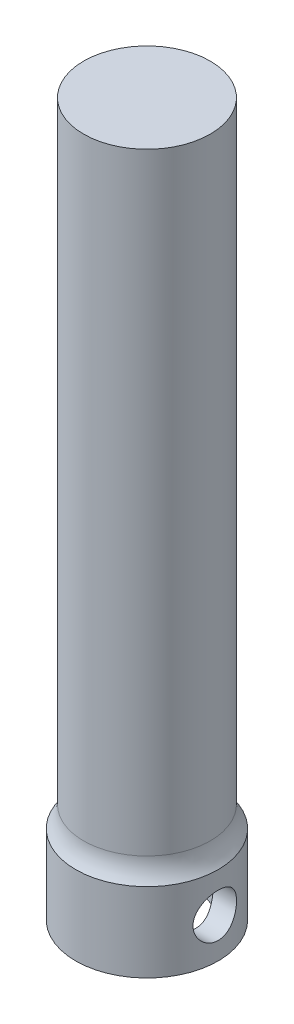
SolidWorks part; units mm, degrees
ref_plane "Front Plane" through (0, 0, 0) normal (0, 0, 1) x (1, 0, 0)
ref_plane "Top Plane" through (0, 0, 0) normal (0, 1, 0) x (1, 0, 0)
ref_plane "Right Plane" through (0, 0, 0) normal (1, 0, 0) x (0, 0, -1)
sketch "Sketch1" plane through (0, 0, 0) normal (0, 1, 0) x (1, 0, 0)
  line L0 (-4.0996, 3) -> (4.0996, 3)
  arc A0 (-4.0996, 3) -> (4.0996, 3) centre (0, 0) ccw
  dimension "D1" = 10.16
  dimension "D2" = 3
extrude "Boss-Extrude1" add sketch "Sketch1" along normal blind 57.15
sketch "Sketch3" plane through (0, 0, 0) normal (0, -1, 0) x (1, 0, 0)
  line L0 (-4.0996, -3) -> (4.0996, -3)
  arc A0 (-4.0996, -3) -> (4.0996, -3) centre (0, 0) ccw
extrude "Boss-Extrude2" add sketch "Sketch3" against normal up to surface (57.15 mm away) up to face at (0, 57.15, 1.04)
sketch "Sketch4" plane through (0, 57.15, 0) normal (0, 1, 0) x (1, 0, 0)
  line L1 (-4.0996, 3) -> (4.0996, 3)
  arc A0 (-4.0996, 3) -> (4.0996, 3) centre (0, 0) cw
extrude "Boss-Extrude3" add sketch "Sketch4" against normal blind 6.35
sketch "Sketch5" plane through (0, 0, 0) normal (0, -1, 0) x (1, 0, 0)
  circle A0 centre (0, 0) radius 3.9688
  dimension "D1" = 7.9375
extrude "Cut-Extrude1" cut sketch "Sketch5" against normal blind 6.35
ref_plane "Plane1" through (5.08, 0, 0) normal (1, 0, 0) x (0, 0, -1)
ref_plane "Plane2" through (0, 6.35, 0) normal (0, -1, 0) x (-1, 0, 0)
sketch "Sketch7" plane through (0, 6.35, 0) normal (0, -1, 0) x (-1, 0, 0)
  circle A0 centre (0, 0) radius 5.715
  circle A1 centre (0, 0) radius 3.9688
  dimension "D1" = 11.43
extrude "Boss-Extrude4" add sketch "Sketch7" along normal up to surface (6.35 mm away) contours A0 region at (5.5534, 6.35, 0) up to face at (0, 0, -3.9688)
sketch "Sketch6" plane through (5.08, 0, 0) normal (1, 0, 0) x (0, 0, -1)
  circle A0 centre (0, 3.175) radius 1.75
  dimension "D1" = 3.5
  dimension "D2" = 3.175
extrude "Cut-Extrude2" cut sketch "Sketch6" against normal through all both and the other way through all
fillet "Fillet1" radius 2.54 1 edges at (0, 6.35, -5.08)
